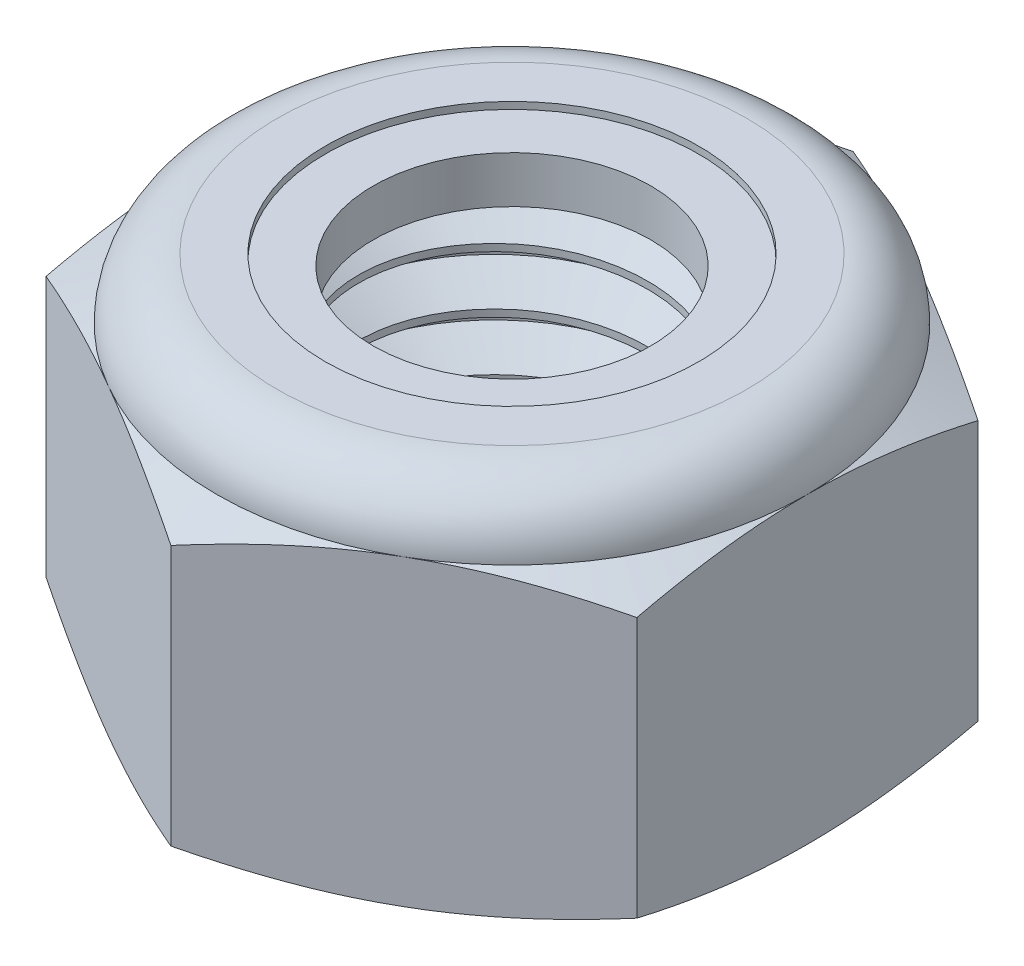
SolidWorks part; units mm, degrees
ref_plane "Front" through (0, 0, 0) normal (0, 0, 1) x (1, 0, 0)
ref_plane "Top" through (0, 0, 0) normal (0, 1, 0) x (1, 0, 0)
ref_plane "Right" through (0, 0, 0) normal (1, 0, 0) x (0, 0, -1)
sketch "Sketch1" plane through (0, 0, 0) normal (0, 1, 0) x (1, 0, 0)
  line L1 (0, 7.5056) -> (-6.5, 3.7528)
  line L2 (-6.5, 3.7528) -> (-6.5, -3.7528)
  line L3 (-6.5, -3.7528) -> (0, -7.5056)
  line L4 (0, -7.5056) -> (6.5, -3.7528)
  line L5 (6.5, -3.7528) -> (6.5, 3.7528)
  line L6 (6.5, 3.7528) -> (0, 7.5056)
  circle A0 centre (0, 0) radius 6.5 construction
  dimension "Hex Flats" = 13
extrude "Extrude1" add sketch "Sketch1" along normal blind 8
sketch "Sketch2" plane through (0, 0, 0) normal (1, 0, 0) x (0, 0, -1)
  line L0 (-4, 0) -> (-4, 8) construction
  line L1 (0, 0) -> (4, 0)
  line L2 (0, 0) -> (0, 8)
  line L3 (0, 8) -> (4, 8)
  line L4 (4, 0) -> (4, 8)
  line L5 (-3.7528, 8) -> (3.7528, 8) construction
  line L7 (0, -4) -> (0, 0) construction
  dimension "Thread Dia" = 8
revolve "Revolve1" add sketch "Sketch2" angle 360 about L7
sketch "Sketch8" plane through (0, 0, 0) normal (0, -1, 0) x (1, 0, 0)
  circle A1 centre (0, 0) radius 4
  circle A2 centre (0, 0) radius 4
  dimension "D1" = 0
curve "Helix/Spiral1" pitch 1.25 height 9.25 turns 7.4 parameters "Pitch"=1.25
sketch "Sketch10" plane through (0, 0, 0) normal (0, -1, 0) x (1, 0, 0)
  circle A1 centre (0, 0) radius 4
  circle A2 centre (0, 0) radius 4
  dimension "D1" = 0
extrude "Boss-Extrude1" add sketch "Sketch10" against normal through all draft 45
sketch "Sketch11" plane through (0, 8, 0) normal (0, 1, 0) x (1, 0, 0)
  circle A1 centre (0, 0) radius 4
  circle A2 centre (0, 0) radius 4
  dimension "D1" = 0
extrude "Boss-Extrude2" add sketch "Sketch11" against normal through all draft 45
sketch "Sketch9" plane through (0, 0, 0) normal (1, 0, 0) x (0, 0, -1)
  line L0 (4, -1.0938) -> (4, 0)
  line L1 (4, -1.0938) -> (3.1881, -0.625)
  line L2 (3.1881, -0.625) -> (3.1881, -0.4688)
  line L3 (3.1881, -0.4688) -> (4, 0)
  line L4 (-4, 0) -> (4, 0) construction
  line L5 (4, -0.5469) -> (3.1881, -0.5469) construction
  line L6 (3.5941, -0.8594) -> (3.5941, -0.2344) construction
  dimension "D1" = 0.1562
  dimension "D2" = 0.625
  dimension "D3" = 60
sweep "Cut-Sweep1" cut profiles "Sketch9" path "Helix/Spiral1"
combine bodies "Combine1" operation type subtract main body 108 bodies to subtract 132
sketch "Sketch5" plane through (0, 0, 0) normal (1, 0, 0) x (0, 0, -1)
  line L0 (0, 0) -> (6.5, 0)
  line L1 (6.5, 0) -> (7.5056, 0.4689)
  line L2 (7.5056, 0.4689) -> (7.5056, 6.1978)
  line L3 (7.5056, 6.1978) -> (6.5, 6.6667)
  line L4 (5.1667, 8) -> (5.1667, 9.27)
  line L5 (5.1667, 9.27) -> (8.7756, 9.27)
  line L6 (8.7756, 9.27) -> (8.7756, -1.27)
  line L7 (8.7756, -1.27) -> (0, -1.27)
  line L8 (0, -1.27) -> (0, 0)
  line L9 (6.5, 6.6667) -> (6.5, 0) construction
  line L10 (0, 0) -> (4, 0) construction
  line L13 (7.5056, 3.3333) -> (8.7756, 3.3333) construction
  line L14 (7.5056, 8) -> (7.5056, 0) construction
  line L15 (0, 0) -> (0, 9.27) construction
  line L20 (0, 9.27) -> (5.1667, 9.27) construction
  line L22 (0, 8) -> (4, 8) construction
  arc A0 (6.5, 6.6667) -> (5.1667, 8) centre (5.1667, 6.6667) ccw
  dimension "D1" = 25
  dimension "D2" = 1.27
  dimension "D3" = 8
  dimension "D4" = 1.3333
revolve "Cut-Revolve3" cut sketch "Sketch5" angle 360 about L15
sketch "Sketch6" plane through (0, 0, 0) normal (1, 0, 0) x (0, 0, -1)
  line L0 (0, 6.6667) -> (6.3476, 6.6667)
  line L1 (5.1667, 7.8476) -> (4.1097, 7.8476)
  line L2 (0, 9.27) -> (0, 6.6667)
  line L3 (4.1097, 9.27) -> (0, 9.27)
  line L4 (0, 9.27) -> (5.1667, 9.27) construction
  line L5 (0, 0) -> (0, 9.27) construction
  line L6 (0, 9.27) -> (0, 0) construction
  line L7 (4.1097, 7.8476) -> (4.1097, 9.27)
  line L8 (5.1667, 8) -> (5.1667, 7.8476) construction
  line L9 (4.1097, 7.8476) -> (3.0528, 7.8476) construction
  line L10 (3.0528, 7.8476) -> (3.0528, 0) construction
  line L13 (3.0528, 7.2969) -> (4, 6.75) construction
  line L15 (4, 0) -> (4, 8) construction
  line L16 (3.0528, 7.4531) -> (4, 8) construction
  line L19 (3.5264, 7.0234) -> (3.5264, 7.7266) construction
  line L20 (3.0528, 7.2969) -> (3.0528, 7.4531) construction
  line L21 (4, 6.75) -> (4, 8) construction
  line L22 (4, 7.375) -> (3.0528, 7.375) construction
  arc A0 (6.3476, 6.6667) -> (5.1667, 7.8476) centre (5.1667, 6.6667) ccw
  arc A1 (6.5, 6.6667) -> (5.1667, 8) centre (5.1667, 6.6667) ccw construction
  dimension "D1" = 0.1524
  dimension "D2" = 1.25
  dimension "D3" = 0.1562
  dimension "D4" = 60
revolve "Cut-Revolve4" cut sketch "Sketch6" angle 360 about L6
sketch "Sketch7" plane through (0, 0, 0) normal (1, 0, 0) x (0, 0, -1)
  line L0 (3.0528, 6.7429) -> (6.2688, 6.7429)
  line L1 (5.1667, 7.7714) -> (3.0528, 7.7714)
  line L2 (3.0528, 7.7714) -> (3.0528, 6.7429)
  line L3 (3.0528, 6.7429) -> (0, 6.7429) construction
  line L4 (0, 6.7429) -> (0, 7.7714) construction
  line L5 (0, 7.7714) -> (3.0528, 7.7714) construction
  line L6 (3.0528, 6.7429) -> (3.0528, 6.6667) construction
  line L7 (0, 6.6667) -> (6.3476, 6.6667) construction
  line L8 (5.1667, 7.7714) -> (5.1667, 7.8476) construction
  line L9 (3.0528, 7.8476) -> (3.0528, 0) construction
  arc A0 (6.2688, 6.7429) -> (5.1667, 7.7714) centre (5.1667, 6.6667) ccw
  arc A2 (6.3476, 6.6667) -> (5.1667, 7.8476) centre (5.1667, 6.6667) ccw construction
  dimension "D1" = 0.0762
revolve "Revolve2" add sketch "Sketch7" angle 360 about L4
equation "\"D4@Sketch5\"=\"Height@Extrude1\"/6"
equation "\"D3@Helix/Spiral1\"=\"Pitch@Helix/Spiral1\"+\"Height@Extrude1\""
equation "\"D1@Sketch9\"=\"Pitch@Helix/Spiral1\"*.125"
equation "\"D2@Sketch9\"=\"Pitch@Helix/Spiral1\"*.50"
equation "\"D2@Sketch6\"=\"Pitch@Helix/Spiral1\""
equation "\"D3@Sketch6\"=\"Pitch@Helix/Spiral1\"/8"
